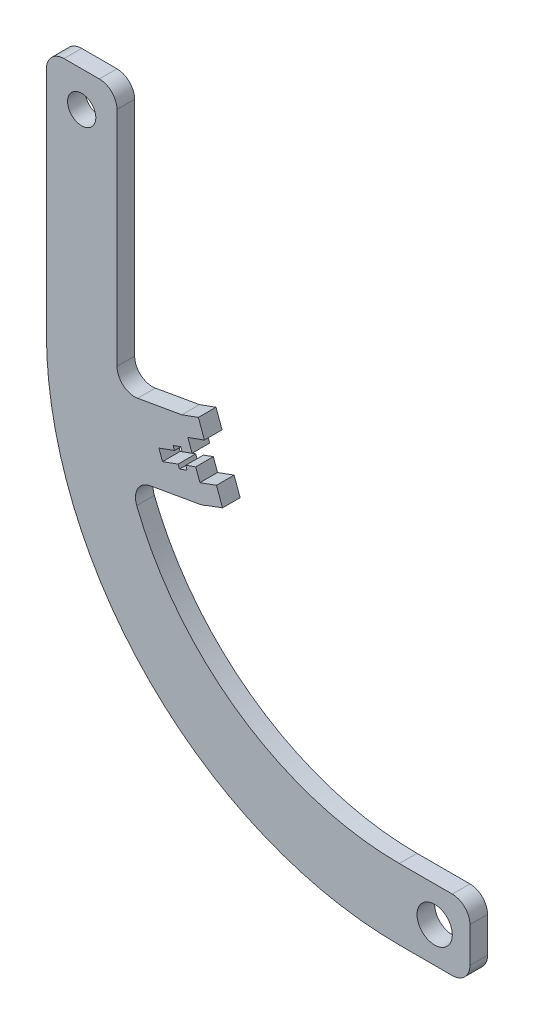
SolidWorks part; units mm, degrees
ref_plane "Front Plane" through (0, 0, 0) normal (0, 0, 1) x (1, 0, 0)
ref_plane "Top Plane" through (0, 0, 0) normal (0, 1, 0) x (1, 0, 0)
ref_plane "Right Plane" through (0, 0, 0) normal (1, 0, 0) x (0, 0, -1)
sketch "Sketch1" plane through (0, 0, 0) normal (0, 0, 1) x (1, 0, 0)
  line L0 (-10, 10) -> (10, 10)
  line L1 (10, 10) -> (10, -10)
  line L2 (10, -10) -> (-10, -10)
  line L4 (-110, 90) -> (-110, 160)
  line L5 (-110, 160) -> (-90, 160)
  line L12 (0, 0) -> (67.8578, 0) construction
  line L13 (-85.9774, 80) -> (-110, 80) construction
  line L14 (-100, 160) -> (-100, 80) construction
  line L15 (-90, 160) -> (-90, 90)
  line L17 (0, 0) -> (0, 249.807) construction
  line L18 (-89.9032, 86.0652) -> (-86.4302, 66.369) construction
  line L19 (-86.4302, 66.369) -> (-88.1667, 76.2171) construction
  line L20 (-88.1667, 76.2171) -> (-27.8813, 86.8471) construction
  line L22 (-72.6652, 92.1032) -> (-64.7993, 70.4917) construction
  line L24 (-68.2195, 79.8886) -> (-74.7903, 77.497) construction
  line L25 (-67.7064, 78.4791) -> (-66.5094, 75.1901)
  line L26 (-61.8109, 76.9002) -> (-60.1008, 72.2018)
  line L27 (-60.1008, 72.2018) -> (-64.7993, 70.4917)
  line L28 (-61.8109, 76.9002) -> (-66.5094, 75.1901)
  line L29 (-68.7325, 81.2981) -> (-69.9296, 84.5871)
  line L30 (-69.9296, 84.5871) -> (-65.2311, 86.2972)
  line L31 (-65.2311, 86.2972) -> (-66.9412, 90.9956)
  line L32 (-66.9412, 90.9956) -> (-71.6397, 89.2855)
  line L33 (-67.7064, 78.4791) -> (-68.7325, 81.2981) construction
  line L34 (-68.7325, 81.2981) -> (-71.5516, 80.2721)
  line L35 (-73.7129, 79.4854) -> (-74.0891, 80.5191)
  line L36 (-70.1493, 76.4193) -> (-72.3106, 75.6327)
  line L37 (-71.9278, 81.3057) -> (-71.5516, 80.2721)
  line L38 (-73.7129, 79.4854) -> (-78.1294, 77.8779)
  line L39 (-78.1294, 77.8779) -> (-77.1034, 75.0589)
  line L40 (-77.1034, 75.0589) -> (-72.6868, 76.6664)
  line L41 (-70.5255, 77.453) -> (-70.1493, 76.4193)
  line L42 (-74.0891, 80.5191) -> (-71.9278, 81.3057)
  line L43 (-72.3106, 75.6327) -> (-72.6868, 76.6664)
  line L44 (-70.5255, 77.453) -> (-67.7064, 78.4791)
  line L45 (-77.6164, 76.4684) -> (-68.2195, 79.8886) construction
  line L47 (-89.9032, 86.0652) -> (-71.6397, 89.2855)
  line L48 (-86.4302, 66.369) -> (-64.6937, 70.2018)
  line L49 (-64.6937, 70.2018) -> (-64.7993, 70.4917)
  circle A0 centre (0, 0) radius 5
  circle A1 centre (-100, 150) radius 4
  arc A3 (-93.1578, 80) -> (41.9046, 115.4226) centre (0, 0) cw construction
  arc A9 (-110, 90) -> (-10, -10) centre (-10, 90) ccw
  arc A10 (-90, 90) -> (-10, 10) centre (-10, 90) ccw construction
  arc A11 (-90, 90) -> (-89.9032, 86.0652) centre (-10, 90) ccw
  arc A12 (-86.4302, 66.369) -> (-10, 10) centre (-10, 90) ccw
  dimension "D1" = 10
  dimension "D13" = 8
  dimension "D7" = 20
  dimension "D2" = 10
  dimension "D3" = 10
  dimension "D4" = 20
  dimension "D5" = 93.1578
  dimension "D6" = 100
  dimension "D8" = 20
  dimension "D9" = 20
  dimension "D10" = 10
  dimension "D11" = 80
  dimension "D12" = 160
  dimension "D14" = 10
  dimension "D15" = 5
  dimension "D16" = 5
  dimension "D17" = 5.2
  dimension "D18" = 3
  dimension "D19" = 2.3
  dimension "D20" = 3
  dimension "D21" = 10
  dimension "D22" = 80
  dimension "D23" = 20
extrude "Boss-Extrude1" add sketch "Sketch1" along normal blind 5
fillet "Fillet3" radius 5 7 edges at (10, -10, 2.5) (10, 10, 2.5) (-90, 160, 2.5) (-110, 160, 2.5) (-64.6937, 70.2018, 2.5) (-86.4302, 66.369, 2.5) (-89.9032, 86.0652, 2.5)
